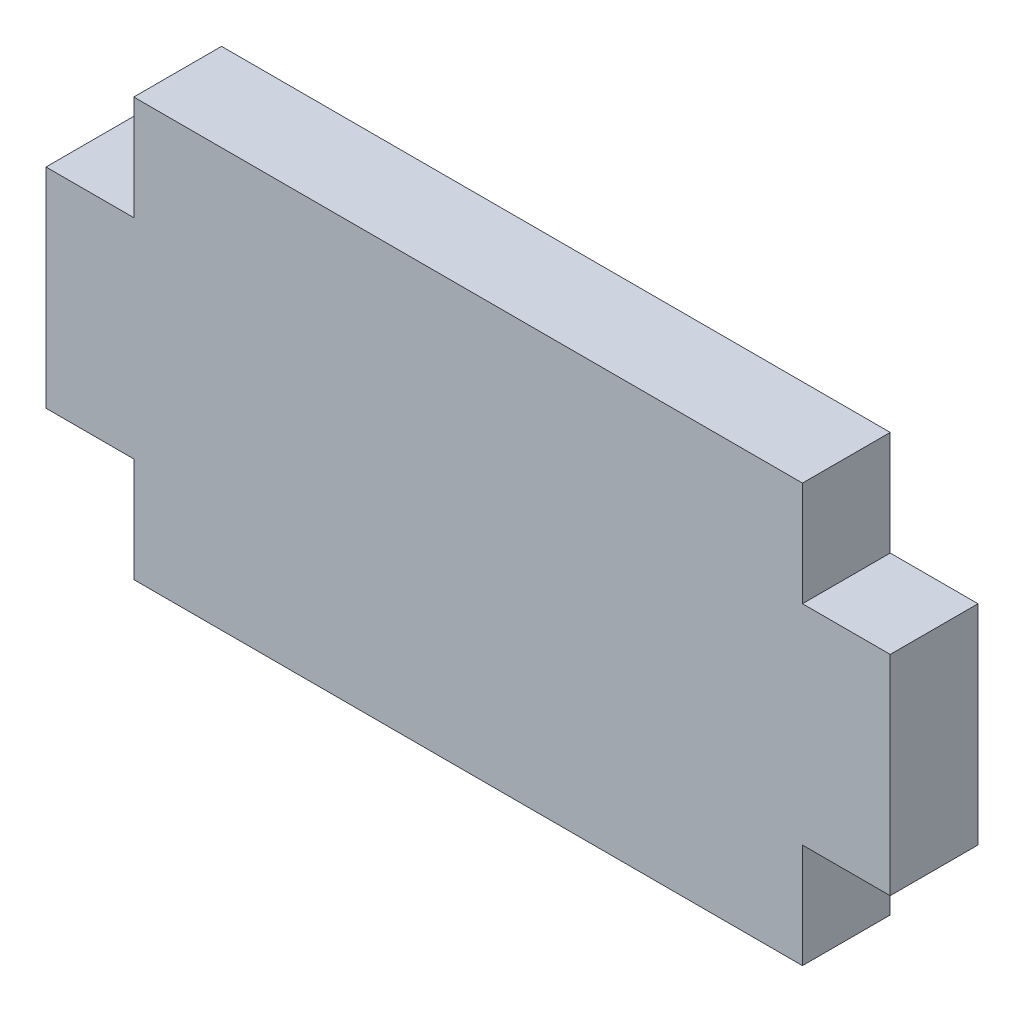
SolidWorks part; units mm, degrees
ref_plane "Front Plane" through (0, 0, 0) normal (0, 0, 1) x (1, 0, 0)
ref_plane "Top Plane" through (0, 0, 0) normal (0, 1, 0) x (1, 0, 0)
ref_plane "Right Plane" through (0, 0, 0) normal (1, 0, 0) x (0, 0, -1)
sketch "Sketch1" plane through (0, 0, 0) normal (0, 0, 1) x (1, 0, 0)
  line L1 (-112.0788, 6.6833) -> (-60.7708, 6.6833)
  line L2 (-112.0788, 6.6833) -> (-112.0788, -18.7167)
  line L3 (-112.0788, -18.7167) -> (-60.7708, -18.7167)
  line L4 (-60.7708, 6.6833) -> (-60.7708, -18.7167)
  dimension "D1" = 25.4
  dimension "D2" = 51.308
extrude "Boss-Extrude1" add sketch "Sketch1" along normal blind 5.334
sketch "Sketch2" plane through (0, 0, 5.334) normal (0, 0, 1) x (1, 0, 0)
  line L1 (-66.1048, -18.7167) -> (-66.1048, -12.3667)
  line L2 (-112.0788, 6.6833) -> (-106.7448, 6.6833)
  line L3 (-112.0788, 6.6833) -> (-112.0788, 0.3333)
  line L4 (-112.0788, 0.3333) -> (-106.7448, 0.3333)
  line L5 (-106.7448, 6.6833) -> (-106.7448, 0.3333)
  line L7 (-60.7708, 6.6833) -> (-112.0788, 6.6833) construction
  line L9 (-112.0788, -18.7167) -> (-106.7448, -18.7167)
  line L10 (-112.0788, -18.7167) -> (-60.7708, -18.7167) construction
  line L11 (-86.4248, 6.6833) -> (-86.4248, -18.7167) construction
  line L12 (-112.0788, -18.7167) -> (-112.0788, -12.3667)
  line L13 (-112.0788, -12.3667) -> (-106.7448, -12.3667)
  line L14 (-106.7448, -18.7167) -> (-106.7448, -12.3667)
  line L15 (-60.7708, -12.3667) -> (-66.1048, -12.3667)
  line L16 (-60.7708, -18.7167) -> (-60.7708, -12.3667)
  line L17 (-60.7708, -18.7167) -> (-66.1048, -18.7167)
  line L18 (-66.1048, 6.6833) -> (-66.1048, 0.3333)
  line L19 (-60.7708, 0.3333) -> (-66.1048, 0.3333)
  line L20 (-60.7708, 6.6833) -> (-60.7708, 0.3333)
  line L21 (-60.7708, 6.6833) -> (-66.1048, 6.6833)
  dimension "D1" = 5.334
  dimension "D2" = 6.35
  dimension "D3" = 6.35
  dimension "D4" = 5.334
extrude "Cut-Extrude1" cut sketch "Sketch2" against normal through all
equation "\"MDF\"= .21in"
equation "\"Foamcore\"= .13in"
equation "\"Gmaterial\"= \"MDF\""
equation "\"D1@Boss-Extrude1\"=\"MDF\""
equation "\"D1@Sketch2\"=\"MDF\""
equation "\"D4@Sketch2\"=\"MDF\""
